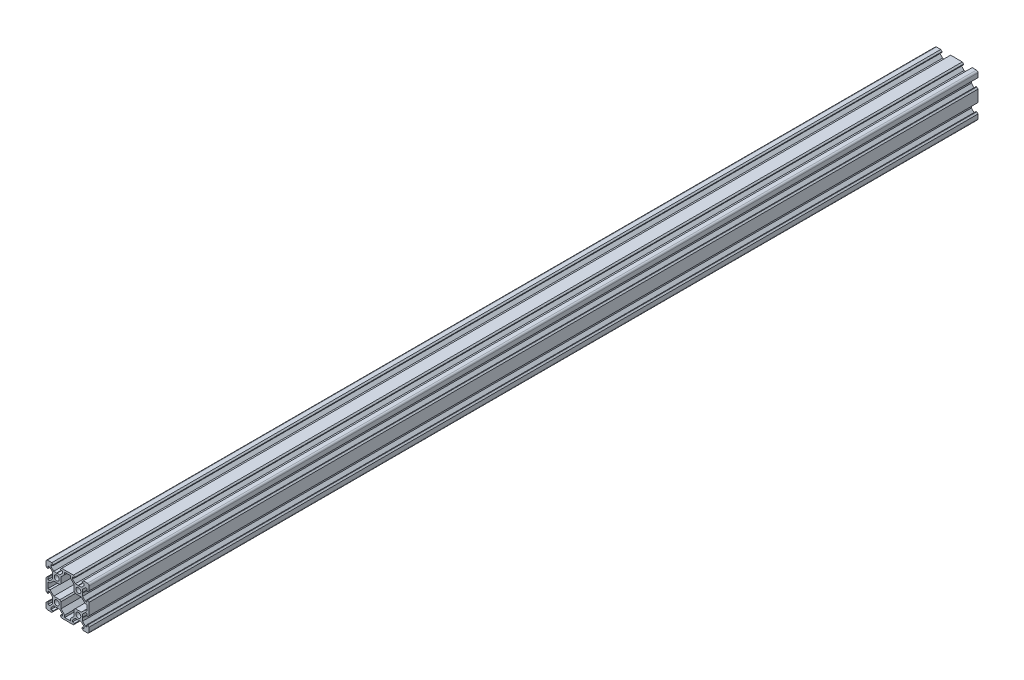
SolidWorks part; units mm, degrees
material "6063-T5"
ref_plane "Front Plane" through (0, 0, 0) normal (0, 0, 1) x (1, 0, 0)
ref_plane "Top Plane" through (0, 0, 0) normal (0, 1, 0) x (1, 0, 0)
ref_plane "Right Plane" through (0, 0, 0) normal (1, 0, 0) x (0, 0, -1)
sketch "Sketch1" plane through (0, 0, 0) normal (0, 0, 1) x (1, 0, 0)
  line L1 (18.5, -20) -> (-18.5, -20)
  line L2 (20, -18.5) -> (20, 18.5)
  line L3 (18.5, 20) -> (-18.5, 20)
  line L4 (-20, -18.5) -> (-20, 18.5)
  line L5 (20, -20) -> (-20, 20) construction
  line L6 (20, 20) -> (-20, -20) construction
  circle A0 centre (-10, 10) radius 2.3
  circle A1 centre (10, -10) radius 2.3
  circle A2 centre (10, 10) radius 2.3
  circle A3 centre (-10, -10) radius 2.3
  arc A4 (-18.5, -20) -> (-20, -18.5) centre (-18.5, -18.5) cw
  arc A5 (18.5, -20) -> (20, -18.5) centre (18.5, -18.5) ccw
  arc A6 (20, 18.5) -> (18.5, 20) centre (18.5, 18.5) ccw
  arc A7 (-18.5, 20) -> (-20, 18.5) centre (-18.5, 18.5) ccw
  point P0 (0, 0)
  line B0 (-10, 10) -> (-10, 20) construction
  line B1 (-10, 13.69) -> (-10.21, 13.9)
  line B2 (-10.21, 13.9) -> (-12.8393, 13.9)
  line B3 (-12.8393, 13.9) -> (-15.5, 16.5607)
  line B4 (-15.5, 16.5607) -> (-15.5, 18.2)
  line B5 (-15.5, 18.2) -> (-13.395, 18.2)
  line B6 (-13.395, 18.2) -> (-13.395, 18.815)
  line B7 (-13.395, 18.815) -> (-14.58, 20)
  line B8 (-14.58, 20) -> (-5.42, 20)
  line B9 (-10, 10) -> (-15.9132, 15.9132) construction
  line B10 (-6.605, 18.815) -> (-5.42, 20)
  line B11 (-6.605, 18.2) -> (-6.605, 18.815)
  line B12 (-4.5, 18.2) -> (-6.605, 18.2)
  line B13 (-4.5, 16.5607) -> (-4.5, 18.2)
  line B14 (-7.1607, 13.9) -> (-4.5, 16.5607)
  line B15 (-9.79, 13.9) -> (-7.1607, 13.9)
  line B16 (-10, 13.69) -> (-9.79, 13.9)
  line B17 (10, 10) -> (10, 20) construction
  line B18 (10, 13.69) -> (9.79, 13.9)
  line B19 (9.79, 13.9) -> (7.1607, 13.9)
  line B20 (7.1607, 13.9) -> (4.5, 16.5607)
  line B21 (4.5, 16.5607) -> (4.5, 18.2)
  line B22 (4.5, 18.2) -> (6.605, 18.2)
  line B23 (6.605, 18.2) -> (6.605, 18.815)
  line B24 (6.605, 18.815) -> (5.42, 20)
  line B25 (5.42, 20) -> (14.58, 20)
  line B26 (10, 10) -> (4.0868, 15.9132) construction
  line B27 (13.395, 18.815) -> (14.58, 20)
  line B28 (13.395, 18.2) -> (13.395, 18.815)
  line B29 (15.5, 18.2) -> (13.395, 18.2)
  line B30 (15.5, 16.5607) -> (15.5, 18.2)
  line B31 (12.8393, 13.9) -> (15.5, 16.5607)
  line B32 (10.21, 13.9) -> (12.8393, 13.9)
  line B33 (10, 13.69) -> (10.21, 13.9)
  line B34 (-10, 10) -> (-20, 10) construction
  line B35 (-13.69, 10) -> (-13.9, 9.79)
  line B36 (-13.9, 9.79) -> (-13.9, 7.1607)
  line B37 (-13.9, 7.1607) -> (-16.5607, 4.5)
  line B38 (-16.5607, 4.5) -> (-18.2, 4.5)
  line B39 (-18.2, 4.5) -> (-18.2, 6.605)
  line B40 (-18.2, 6.605) -> (-18.815, 6.605)
  line B41 (-18.815, 6.605) -> (-20, 5.42)
  line B42 (-20, 5.42) -> (-20, 14.58)
  line B43 (-10, 10) -> (-15.9132, 4.0868) construction
  line B44 (-18.815, 13.395) -> (-20, 14.58)
  line B45 (-18.2, 13.395) -> (-18.815, 13.395)
  line B46 (-18.2, 15.5) -> (-18.2, 13.395)
  line B47 (-16.5607, 15.5) -> (-18.2, 15.5)
  line B48 (-13.9, 12.8393) -> (-16.5607, 15.5)
  line B49 (-13.9, 10.21) -> (-13.9, 12.8393)
  line B50 (-13.69, 10) -> (-13.9, 10.21)
  line B51 (-10, -10) -> (-20, -10) construction
  line B52 (-13.69, -10) -> (-13.9, -10.21)
  line B53 (-13.9, -10.21) -> (-13.9, -12.8393)
  line B54 (-13.9, -12.8393) -> (-16.5607, -15.5)
  line B55 (-16.5607, -15.5) -> (-18.2, -15.5)
  line B56 (-18.2, -15.5) -> (-18.2, -13.395)
  line B57 (-18.2, -13.395) -> (-18.815, -13.395)
  line B58 (-18.815, -13.395) -> (-20, -14.58)
  line B59 (-20, -14.58) -> (-20, -5.42)
  line B60 (-10, -10) -> (-15.9132, -15.9132) construction
  line B61 (-18.815, -6.605) -> (-20, -5.42)
  line B62 (-18.2, -6.605) -> (-18.815, -6.605)
  line B63 (-18.2, -4.5) -> (-18.2, -6.605)
  line B64 (-16.5607, -4.5) -> (-18.2, -4.5)
  line B65 (-13.9, -7.1607) -> (-16.5607, -4.5)
  line B66 (-13.9, -9.79) -> (-13.9, -7.1607)
  line B67 (-13.69, -10) -> (-13.9, -9.79)
  line B68 (-10, -10) -> (-10, -20) construction
  line B69 (-10, -13.69) -> (-9.79, -13.9)
  line B70 (-9.79, -13.9) -> (-7.1607, -13.9)
  line B71 (-7.1607, -13.9) -> (-4.5, -16.5607)
  line B72 (-4.5, -16.5607) -> (-4.5, -18.2)
  line B73 (-4.5, -18.2) -> (-6.605, -18.2)
  line B74 (-6.605, -18.2) -> (-6.605, -18.815)
  line B75 (-6.605, -18.815) -> (-5.42, -20)
  line B76 (-5.42, -20) -> (-14.58, -20)
  line B77 (-10, -10) -> (-4.0868, -15.9132) construction
  line B78 (-13.395, -18.815) -> (-14.58, -20)
  line B79 (-13.395, -18.2) -> (-13.395, -18.815)
  line B80 (-15.5, -18.2) -> (-13.395, -18.2)
  line B81 (-15.5, -16.5607) -> (-15.5, -18.2)
  line B82 (-12.8393, -13.9) -> (-15.5, -16.5607)
  line B83 (-10.21, -13.9) -> (-12.8393, -13.9)
  line B84 (-10, -13.69) -> (-10.21, -13.9)
  line B85 (10, -10) -> (10, -20) construction
  line B86 (10, -13.69) -> (10.21, -13.9)
  line B87 (10.21, -13.9) -> (12.8393, -13.9)
  line B88 (12.8393, -13.9) -> (15.5, -16.5607)
  line B89 (15.5, -16.5607) -> (15.5, -18.2)
  line B90 (15.5, -18.2) -> (13.395, -18.2)
  line B91 (13.395, -18.2) -> (13.395, -18.815)
  line B92 (13.395, -18.815) -> (14.58, -20)
  line B93 (14.58, -20) -> (5.42, -20)
  line B94 (10, -10) -> (15.9132, -15.9132) construction
  line B95 (6.605, -18.815) -> (5.42, -20)
  line B96 (6.605, -18.2) -> (6.605, -18.815)
  line B97 (4.5, -18.2) -> (6.605, -18.2)
  line B98 (4.5, -16.5607) -> (4.5, -18.2)
  line B99 (7.1607, -13.9) -> (4.5, -16.5607)
  line B100 (9.79, -13.9) -> (7.1607, -13.9)
  line B101 (10, -13.69) -> (9.79, -13.9)
  line B102 (10, 10) -> (20, 10) construction
  line B103 (13.69, 10) -> (13.9, 10.21)
  line B104 (13.9, 10.21) -> (13.9, 12.8393)
  line B105 (13.9, 12.8393) -> (16.5607, 15.5)
  line B106 (16.5607, 15.5) -> (18.2, 15.5)
  line B107 (18.2, 15.5) -> (18.2, 13.395)
  line B108 (18.2, 13.395) -> (18.815, 13.395)
  line B109 (18.815, 13.395) -> (20, 14.58)
  line B110 (20, 14.58) -> (20, 5.42)
  line B111 (10, 10) -> (15.9132, 15.9132) construction
  line B112 (18.815, 6.605) -> (20, 5.42)
  line B113 (18.2, 6.605) -> (18.815, 6.605)
  line B114 (18.2, 4.5) -> (18.2, 6.605)
  line B115 (16.5607, 4.5) -> (18.2, 4.5)
  line B116 (13.9, 7.1607) -> (16.5607, 4.5)
  line B117 (13.9, 9.79) -> (13.9, 7.1607)
  line B118 (13.69, 10) -> (13.9, 9.79)
  line B119 (10, -10) -> (20, -10) construction
  line B120 (13.69, -10) -> (13.9, -9.79)
  line B121 (13.9, -9.79) -> (13.9, -7.1607)
  line B122 (13.9, -7.1607) -> (16.5607, -4.5)
  line B123 (16.5607, -4.5) -> (18.2, -4.5)
  line B124 (18.2, -4.5) -> (18.2, -6.605)
  line B125 (18.2, -6.605) -> (18.815, -6.605)
  line B126 (18.815, -6.605) -> (20, -5.42)
  line B127 (20, -5.42) -> (20, -14.58)
  line B128 (10, -10) -> (15.9132, -4.0868) construction
  line B129 (18.815, -13.395) -> (20, -14.58)
  line B130 (18.2, -13.395) -> (18.815, -13.395)
  line B131 (18.2, -15.5) -> (18.2, -13.395)
  line B132 (16.5607, -15.5) -> (18.2, -15.5)
  line B133 (13.9, -12.8393) -> (16.5607, -15.5)
  line B134 (13.9, -10.21) -> (13.9, -12.8393)
  line B135 (13.69, -10) -> (13.9, -10.21)
  line B136 (-18.2, -2.7) -> (-18.2, 2.7)
  line B137 (-18.2, 2.7) -> (-16.2393, 2.7)
  line B138 (-16.2393, 2.7) -> (-12.8393, 6.1)
  line B139 (-12.8393, 6.1) -> (-7.1607, 6.1)
  line B140 (-10, 6.1) -> (-10, 0) construction
  line B141 (-10, 0) -> (-18.2, 0) construction
  line B142 (-12.8393, -6.1) -> (-7.1607, -6.1)
  line B143 (-16.2393, -2.7) -> (-12.8393, -6.1)
  line B144 (-18.2, -2.7) -> (-16.2393, -2.7)
  line B145 (-10, 6.1) -> (-10, 10) construction
  line B146 (-10, 10) -> (-15.0927, 4.9073) construction
  line B147 (-10, 10) -> (-6.3747, 6.3747) construction
  line B148 (2.7, 18.2) -> (2.7, 16.2393)
  line B149 (2.7, 16.2393) -> (6.1, 12.8393)
  line B150 (6.1, 12.8393) -> (6.1, 7.1607)
  line B151 (-6.1, 12.8393) -> (-6.1, 7.1607)
  line B152 (-2.7, 16.2393) -> (-6.1, 12.8393)
  line B153 (-2.7, 18.2) -> (-2.7, 16.2393)
  line B154 (2.7, 18.2) -> (-2.7, 18.2)
  line B155 (2.7, -18.2) -> (-2.7, -18.2)
  line B156 (-2.7, -18.2) -> (-2.7, -16.2393)
  line B157 (-2.7, -16.2393) -> (-6.1, -12.8393)
  line B158 (-6.1, -12.8393) -> (-6.1, -7.1607)
  line B159 (6.1, -12.8393) -> (6.1, -7.1607)
  line B160 (2.7, -16.2393) -> (6.1, -12.8393)
  line B161 (2.7, -18.2) -> (2.7, -16.2393)
  line B162 (0, 18.2) -> (0, -18.2) construction
  line B163 (12.8393, -6.1) -> (7.1607, -6.1)
  line B164 (16.2393, -2.7) -> (12.8393, -6.1)
  line B165 (18.2, -2.7) -> (16.2393, -2.7)
  line B166 (18.2, -2.7) -> (18.2, 2.7)
  line B167 (18.2, 2.7) -> (16.2393, 2.7)
  line B168 (16.2393, 2.7) -> (12.8393, 6.1)
  line B169 (12.8393, 6.1) -> (7.1607, 6.1)
  line B170 (-7.1607, 6.1) -> (-6.1, 7.1607)
  line B171 (6.1, 7.1607) -> (7.1607, 6.1)
  line B172 (7.1607, -6.1) -> (6.1, -7.1607)
  line B173 (-6.1, -7.1607) -> (-7.1607, -6.1)
  dimension "D4" = 4.6
  dimension "D5" = 1.5
  dimension "D1" = 40
  dimension "D2" = 10
  dimension "D3" = 10
sketch_block_instance "V Slot 2-1"
sketch_block "V Slot 2" parameters "D1"=10, "D2"=11, "D3"=4.3, "D4"=1.8, "D5"=0.21, "D6"=45, "D7"=9.16, "D8"=1.5, "D9"=6.79
sketch_block_instance "V Slot 2-2"
sketch_block_instance "V Slot 2-3"
sketch_block_instance "V Slot 2-4"
sketch_block_instance "V Slot 2-5"
sketch_block_instance "V Slot 2-6"
sketch_block_instance "V Slot 2-7"
sketch_block_instance "V Slot 2-8"
sketch_block_instance "Center Cutout 2-1"
sketch_block "Center Cutout 2" parameters "D1"=5.4, "D2"=12.2, "D3"=8.2, "D4"=45, "D5"=10, "D6"=1.5
extrude "Boss-Extrude1" add sketch "Sketch1" along normal blind 825 contours B135 B120 B121 B122 B123 B124 B125 B126 L2 B112 B113 B114 B115 B116 B117 B118 B103 B104 B105 B106 B107 B108 B109 A6 L3 B27 B28 B29 B30 B31 B32 B33 B18 B19 B20 B21 B22 B23 B24 B10 B11 B12 B13 B14 B15 B16 B1 B2 B3 region at (16.54, -19.4343, 0)
ref_plane "Plane1" through (0, 0, 412.5) normal (0, 0, 1) x (1, 0, 0)
sketch "Sketch2" plane through (0, 0, 825) normal (0, 0, 1) x (1, 0, 0)
  point P0 (0, 0)
ref_axis "Axis1" through (0, 0, 825) along (0, 0, -1)
